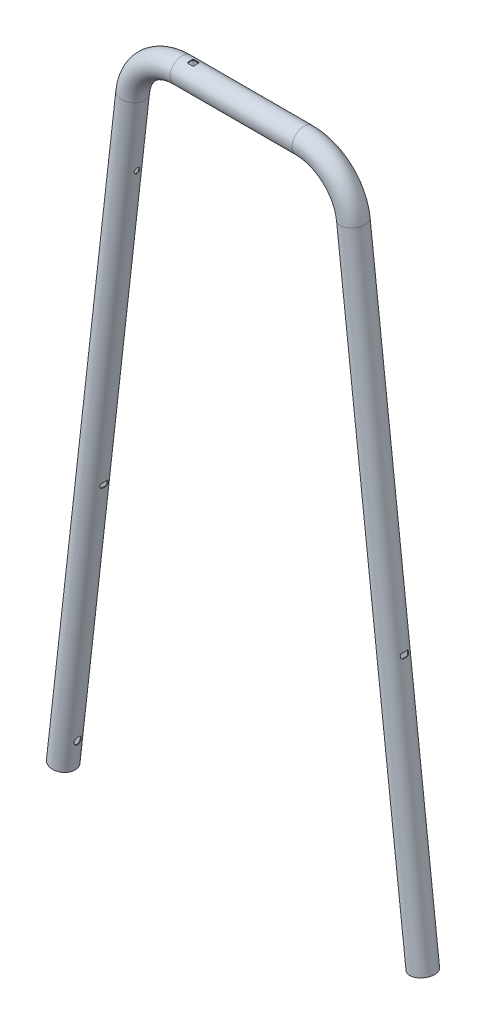
SolidWorks part; units mm, degrees
ref_plane "Front Plane" through (0, 0, 0) normal (0, 0, 1) x (1, 0, 0)
ref_plane "Top Plane" through (0, 0, 0) normal (0, 1, 0) x (1, 0, 0)
ref_plane "Right Plane" through (0, 0, 0) normal (1, 0, 0) x (0, 0, -1)
sketch "Sketch1" plane through (0, 0, 0) normal (0, 0, 1) x (1, 0, 0)
  line L0 (0, 0) -> (0, 595.2821) construction
  line L1 (0, 0) -> (414.971, 0) construction
  line L2 (-67.5, 567.016) -> (67.5, 567.016)
  line L3 (122.1519, 518.1945) -> (199.0811, -162.284)
  line L4 (-122.1519, 518.1945) -> (-199.0811, -162.284)
  line L5 (-199.0811, -162.284) -> (-303.926, -162.284) construction
  arc A0 (122.1519, 518.1945) -> (67.5, 567.016) centre (67.5, 512.016) ccw
  arc A1 (-122.1519, 518.1945) -> (-67.5, 567.016) centre (-67.5, 512.016) cw
  point P12 (116.6325, 567.016)
  point P17 (0, 567.016)
  dimension "D4" = 55
  dimension "D1" = 135
  dimension "D2" = 12.9
  dimension "D3" = 729.3
ref_plane "Plane1" through (-199.0811, -162.284, 0) normal (-0.1123, -0.9937, 0) x (-0.9937, 0.1123, 0)
sketch "Sketch2" plane through (-199.0811, -162.284, 0) normal (-0.1123, -0.9937, 0) x (-0.9937, 0.1123, 0)
  circle A0 centre (0, 0) radius 13.2
  circle A1 centre (0, 0) radius 12.4
  dimension "D1" = 0.8
  dimension "D2" = 26.4
sweep "Sweep2" add profiles "Sketch2" path "Sketch1"
sketch "Sketch6" plane through (-20.6272, -182.4585, 0) normal (-0.1123, -0.9937, 0) x (0.9937, -0.1123, 0)
  line L0 (-179.5906, 0) -> (-191.9906, 0)
  line L1 (-179.5906, 0) -> (-179.5906, 12.4)
  circle A0 centre (-179.5906, 0) radius 12.4 construction
  circle A1 centre (-179.5906, 0) radius 12.4 construction
ref_plane "Plane3" through (-199.0811, -162.284, 0) normal (-0.9937, 0.1123, 0) x (0, 0, 1)
ref_plane "Plane4" through (0, 580.216, 0) normal (0, 1, 0) x (1, 0, 0)
sketch "Sketch17" plane through (-199.0811, -162.284, 0) normal (-0.9937, 0.1123, 0) x (0, 0, 1)
  line L0 (0, 0) -> (0, 30) construction
  line L1 (-13.2, 0) -> (13.2, 0) construction
  line L2 (0, 30) -> (0, 236.8) construction
  circle A0 centre (0, 30) radius 4.05
  dimension "D3" = 8.1
  dimension "D1" = 30
  dimension "D2" = 236.8
extrude "Cut-Extrude6" cut sketch "Sketch17" against normal blind 50
sketch "Sketch18" plane through (-199.0811, -162.284, 0) normal (-0.9937, 0.1123, 0) x (0, 0, 1)
  line L0 (0, 0) -> (0, 292) construction
  line L1 (-12.4, 0) -> (12.4, 0) construction
  line L3 (-2.5, 294.75) -> (2.5, 294.75)
  line L4 (-4.5, 292.75) -> (-4.5, 291.25)
  line L5 (-2.5, 289.25) -> (2.5, 289.25)
  line L6 (4.5, 292.75) -> (4.5, 291.25)
  line L7 (-4.5, 294.75) -> (4.5, 289.25) construction
  line L8 (-4.5, 289.25) -> (4.5, 294.75) construction
  arc A0 (-2.5, 289.25) -> (-4.5, 291.25) centre (-2.5, 291.25) cw
  arc A1 (4.5, 291.25) -> (2.5, 289.25) centre (2.5, 291.25) cw
  arc A2 (2.5, 294.75) -> (4.5, 292.75) centre (2.5, 292.75) cw
  arc A3 (-2.5, 294.75) -> (-4.5, 292.75) centre (-2.5, 292.75) ccw
  dimension "D3" = 2
  dimension "D1" = 5.5
  dimension "D2" = 9
  dimension "D4" = 292
extrude "Cut-Extrude7" cut sketch "Sketch18" against normal blind 50 and the other way blind 50
mirror "Mirror2" about plane through (0, 0, 0) normal (1, 0, 0) of "Cut-Extrude6", "Cut-Extrude7"
sketch "Sketch19" plane through (-199.0811, -162.284, 0) normal (-0.9937, 0.1123, 0) x (0, 0, 1)
  line L0 (0, 0) -> (0, 513) construction
  line L1 (-12.4, 0) -> (12.4, 0) construction
  circle A0 centre (0, 513) radius 4
  dimension "D2" = 8
  dimension "D1" = 513
extrude "Cut-Extrude8" cut sketch "Sketch19" along normal blind 50
sketch "Sketch20" plane through (0, 580.216, 0) normal (0, 1, 0) x (1, 0, 0)
  line L0 (-212.1976, 0) -> (-54.8519, 0) construction
  circle A0 centre (-54.8519, 0) radius 3.5
  ellipse E0 centre (-199.0811, 0) end of major axis (-199.0811, 13.2) minor radius 13.1164 construction
  ellipse E1 centre (-122.1519, 0) end of major axis (-122.1519, 13.2) minor radius 13.1164 construction
  dimension "D2" = 7
  dimension "D1" = 67.3
extrude "Cut-Extrude9" cut sketch "Sketch20" against normal blind 50
sketch "Sketch21" plane through (0, 580.216, 0) normal (0, 1, 0) x (1, 0, 0)
  line L0 (-212.1976, 0) -> (-54.8519, 0) construction
  line L2 (-57.3519, -3.5) -> (-52.3519, -3.5)
  line L3 (-58.3519, -2.5) -> (-58.3519, 2.5)
  line L4 (-57.3519, 3.5) -> (-52.3519, 3.5)
  line L5 (-51.3519, -2.5) -> (-51.3519, 2.5)
  line L6 (-58.3519, -3.5) -> (-51.3519, 3.5) construction
  line L7 (-58.3519, 3.5) -> (-51.3519, -3.5) construction
  arc A0 (-57.3519, 3.5) -> (-58.3519, 2.5) centre (-57.3519, 2.5) ccw
  arc A1 (-58.3519, -2.5) -> (-57.3519, -3.5) centre (-57.3519, -2.5) ccw
  arc A2 (-52.3519, 3.5) -> (-51.3519, 2.5) centre (-52.3519, 2.5) cw
  arc A3 (-51.3519, -2.5) -> (-52.3519, -3.5) centre (-52.3519, -2.5) cw
  ellipse E0 centre (-199.0811, 0) end of major axis (-199.0811, 13.2) minor radius 13.1164 construction
  dimension "D3" = 1
  dimension "D4" = 1
  dimension "D1" = 7
  dimension "D2" = 7
extrude "Cut-Extrude10" cut sketch "Sketch21" against normal blind 10
sketch "Sketch22" plane through (-199.0811, -162.284, 0) normal (-0.9937, 0.1123, 0) x (0, 0, 1)
  line L0 (-12.4, 0) -> (12.4, 0) construction
  circle A0 centre (0, 613) radius 3.05
  dimension "D1" = 613
extrude "Cut-Extrude11" cut sketch "Sketch22" against normal up to next and the other way up to next
